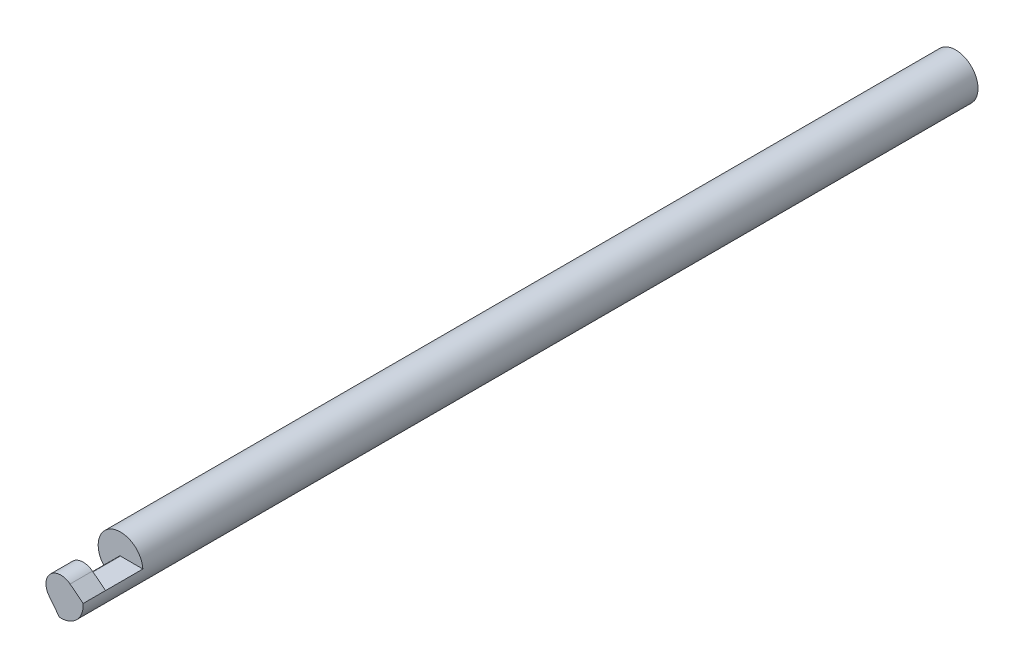
SolidWorks part; units mm, degrees
material "AISI 316 Annealed Stainless Steel Bar (SS)"
ref_plane "Front" through (0, 0, 0) normal (0, 0, 1) x (1, 0, 0)
ref_plane "Top" through (0, 0, 0) normal (0, 1, 0) x (1, 0, 0)
ref_plane "Right" through (0, 0, 0) normal (1, 0, 0) x (0, 0, -1)
ref_axis "X" through (-80.9, 0, 0) along (1, 0, 0)
ref_axis "Y" through (0, -50, 0) along (0, 1, 0)
ref_axis "Z" through (0, 0, -80.9) along (0, 0, 1)
sketch "Sketch1" plane through (0, 0, 0) normal (1, 0, 0) x (0, 0, -1)
  line L0 (0, 0) -> (0, 1.5)
  line L1 (0, 1.5) -> (60, 1.5)
  line L2 (60, 1.5) -> (60, 0)
  line L3 (60, 0) -> (0, 0)
  line L4 (-9.841, 0) -> (-3.2015, 0) construction
  dimension "D1" = 3
  dimension "D2" = 60
revolve "Revolve1" add sketch "Sketch1" angle 360 about L4
sketch "Sketch2" plane through (0, 0, 0) normal (0, 0, 1) x (1, 0, 0)
  line L0 (0, 0.1) -> (1.4967, 0.1)
  line L1 (-0.1, 0) -> (-0.1, -1.4967)
  arc A0 (0, 0.1) -> (-0.1, 0) centre (0, 0) ccw
  circle A2 centre (0, 0) radius 1.5
  arc A3 (1.4967, 0.1) -> (-0.1, -1.4967) centre (0, 0) ccw
  dimension "D2" = 0.1
  dimension "D1" = 0
extrude "Cut-Extrude1" cut sketch "Sketch2" against normal blind 2.5 from offset 1.5 offset against normal yes
sketch "Sketch3" plane through (0, 0, 0) normal (0, 0, 1) x (1, 0, 0)
  line L0 (1.4967, 0.1) -> (0.6155, 0.7881)
  line L1 (-0.1, -1.4967) -> (-0.7881, -0.6155)
  arc A0 (0.6155, 0.7881) -> (-0.7881, -0.6155) centre (0, 0) ccw
  circle A2 centre (0, 0) radius 1.5 construction
  arc A3 (1.4967, 0.1) -> (-0.1, -1.4967) centre (0, 0) ccw
  dimension "D1" = 1
extrude "Cut-Extrude2" cut sketch "Sketch3" against normal up to surface (1.5 mm away) up to face at (-0.1208, 0.1208, -1.5)
